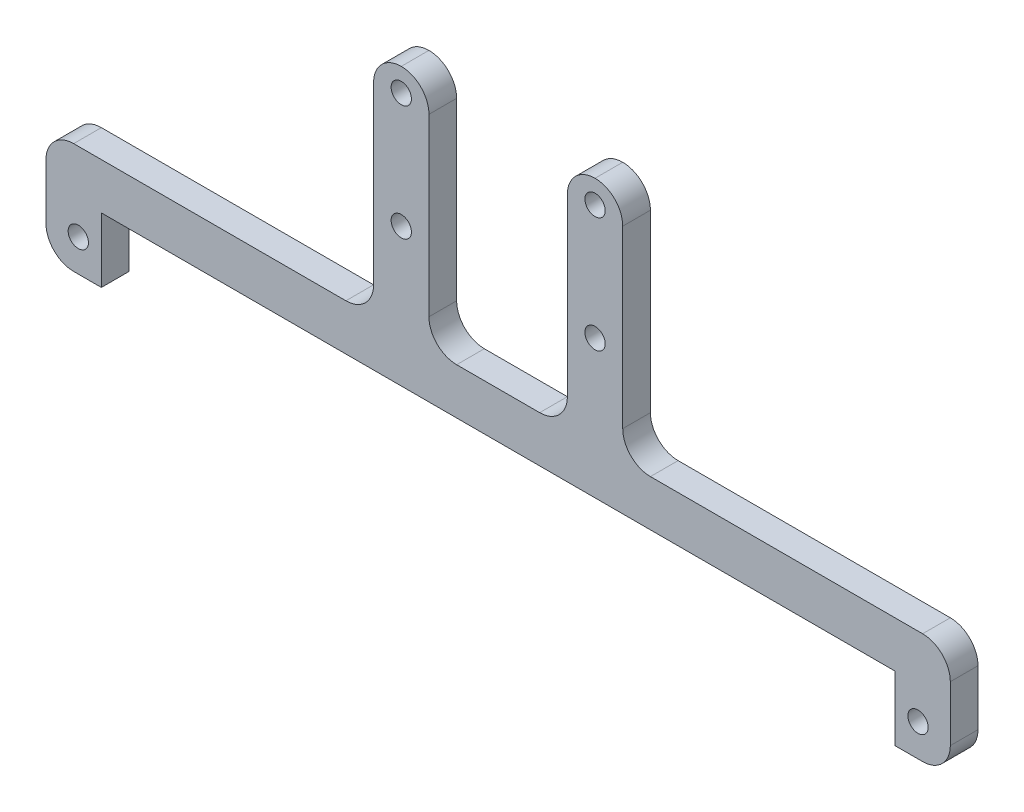
SolidWorks part; units mm, degrees
ref_plane "Plan de face" through (0, 0, 0) normal (0, 0, 1) x (1, 0, 0)
ref_plane "Plan de dessus" through (0, 0, 0) normal (0, 1, 0) x (1, 0, 0)
ref_plane "Plan de droite" through (0, 0, 0) normal (1, 0, 0) x (0, 0, -1)
sketch "Esquisse1" plane through (0, 0, 0) normal (0, 0, 1) x (1, 0, 0)
  line L0 (-13.5, 5) -> (-49, 5)
  line L1 (0, 0) -> (-43, 0)
  line L2 (0, 0) -> (0, 5)
  line L3 (0, 5) -> (-7.5, 5)
  line L4 (-49, 0) -> (-49, 5)
  line L6 (-49, 0) -> (-49, -7)
  line L7 (-49, -7) -> (-43, -7)
  line L8 (-43, 0) -> (-43, -7)
  line L10 (-13.5, 5) -> (-13.5, 30)
  line L11 (-13.5, 30) -> (-7.5, 30)
  line L12 (-7.5, 5) -> (-7.5, 30)
  dimension "D1" = 5
  dimension "D2" = 49
  dimension "D3" = 43
  dimension "D4" = 7
  dimension "D5" = 13.5
  dimension "D6" = 6
  dimension "D7" = 25
extrude "Boss.-Extru.1" add sketch "Esquisse1" along normal blind 3 contours L0 L4 L6 L7 L8 L1 L2 L3 L12 L11 L10
sketch "Esquisse2" plane through (0, 0, 3) normal (0, 0, 1) x (1, 0, 0)
  line L0 (0, 0) -> (0, 5) construction
  line L1 (0, 0) -> (-43, 0) construction
  circle A0 centre (-45.5, -3.5) radius 1.1
  dimension "D1" = 2.2
  dimension "D2" = 45.5
  dimension "D3" = 3.5
extrude "Enlèv. mat.-Extru.1" cut sketch "Esquisse2" against normal blind 3
sketch "Esquisse3" plane through (0, 0, 3) normal (0, 0, 1) x (1, 0, 0)
  line L0 (0, 0) -> (0, 5) construction
  line L1 (0, 5) -> (-7.5, 5) construction
  circle A0 centre (-10.5, 15) radius 1.1
  circle A1 centre (-10.5, 27.5) radius 1.1
  dimension "D1" = 2.2
  dimension "D2" = 2.2
  dimension "D3" = 10.5
  dimension "D4" = 10.5
  dimension "D5" = 10
  dimension "D6" = 12.5
extrude "Enlèv. mat.-Extru.2" cut sketch "Esquisse3" against normal blind 3
fillet "Congé1" radius 3 6 edges at (-13.5, 5, 1.5) (-7.5, 5, 1.5) (-7.5, 30, 1.5) (-13.5, 30, 1.5) (-49, 5, 1.5) (-49, -7, 1.5)
mirror "Symétrie1" about plane through (0, 0, 0) normal (1, 0, 0) of "Congé1", "Enlèv. mat.-Extru.2", "Enlèv. mat.-Extru.1", "Boss.-Extru.1"
